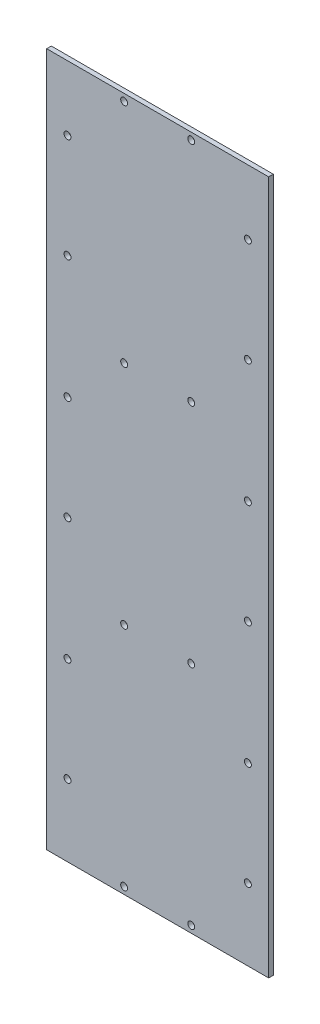
SolidWorks part; units mm, degrees
material "Alumina"
ref_plane "Front Plane" through (0, 0, 0) normal (0, 0, 1) x (1, 0, 0)
ref_plane "Top Plane" through (0, 0, 0) normal (0, 1, 0) x (1, 0, 0)
ref_plane "Right Plane" through (0, 0, 0) normal (1, 0, 0) x (0, 0, -1)
sketch "Sketch1" plane through (0, 0, 0) normal (0, 0, 1) x (1, 0, 0)
  line L1 (48, -150) -> (-48, -150)
  line L2 (48, -150) -> (48, 150)
  line L3 (48, 150) -> (-48, 150)
  line L4 (-48, -150) -> (-48, 150)
  line L5 (48, -150) -> (-48, 150) construction
  line L6 (48, 150) -> (-48, -150) construction
  point P0 (0, 0)
  dimension "D1" = 96
  dimension "D2" = 300
extrude "Boss-Extrude1" add sketch "Sketch1" along normal blind 2
sketch "Sketch2" plane through (0, 0, 2) normal (0, 0, 1) x (1, 0, 0)
  line L0 (-48, 150) -> (-48, -150) construction
  line L1 (48, 150) -> (-48, 150) construction
  line L2 (-48, -150) -> (48, -150) construction
  line L3 (48, -150) -> (48, 150) construction
  line L4 (0, -1.1) -> (0, 1.1) construction
  circle A0 centre (-39, 122) radius 1.5
  circle A1 centre (-39, 77) radius 1.5
  circle A2 centre (39, 122) radius 1.5
  circle A3 centre (39, 77) radius 1.5
  circle A4 centre (-39, 24) radius 1.5
  circle A5 centre (-39, -21) radius 1.5
  circle A6 centre (39, 24) radius 1.5
  circle A7 centre (39, -21) radius 1.5
  circle A8 centre (-39, -74) radius 1.5
  circle A9 centre (-39, -119) radius 1.5
  circle A10 centre (39, -74) radius 1.5
  circle A11 centre (39, -119) radius 1.5
  circle A13 centre (14.5, -147) radius 1.5
  circle A14 centre (-14.5, -147) radius 1.5
  circle A15 centre (-14.5, -49) radius 1.5
  circle A16 centre (14.5, -49) radius 1.5
  circle A17 centre (-14.5, 49) radius 1.5
  circle A18 centre (14.5, 49) radius 1.5
  circle A19 centre (-14.5, 147) radius 1.5
  circle A20 centre (14.5, 147) radius 1.5
  dimension "D1" = 3
  dimension "D3" = 28
  dimension "D4" = 3
  dimension "D6" = 9
  dimension "D10" = 3
  dimension "D11" = 33.5
  dimension "D13" = 3
  dimension "D15" = 9
  dimension "D2" = 9
  dimension "D5" = 45
  dimension "D9" = 31
  dimension "D14" = 9
  dimension "D16" = 3
  dimension "D7" = 2
  dimension "D8" = 3
  dimension "D12" = 4
extrude "Cut-Extrude1" cut sketch "Sketch2" against normal blind 10
